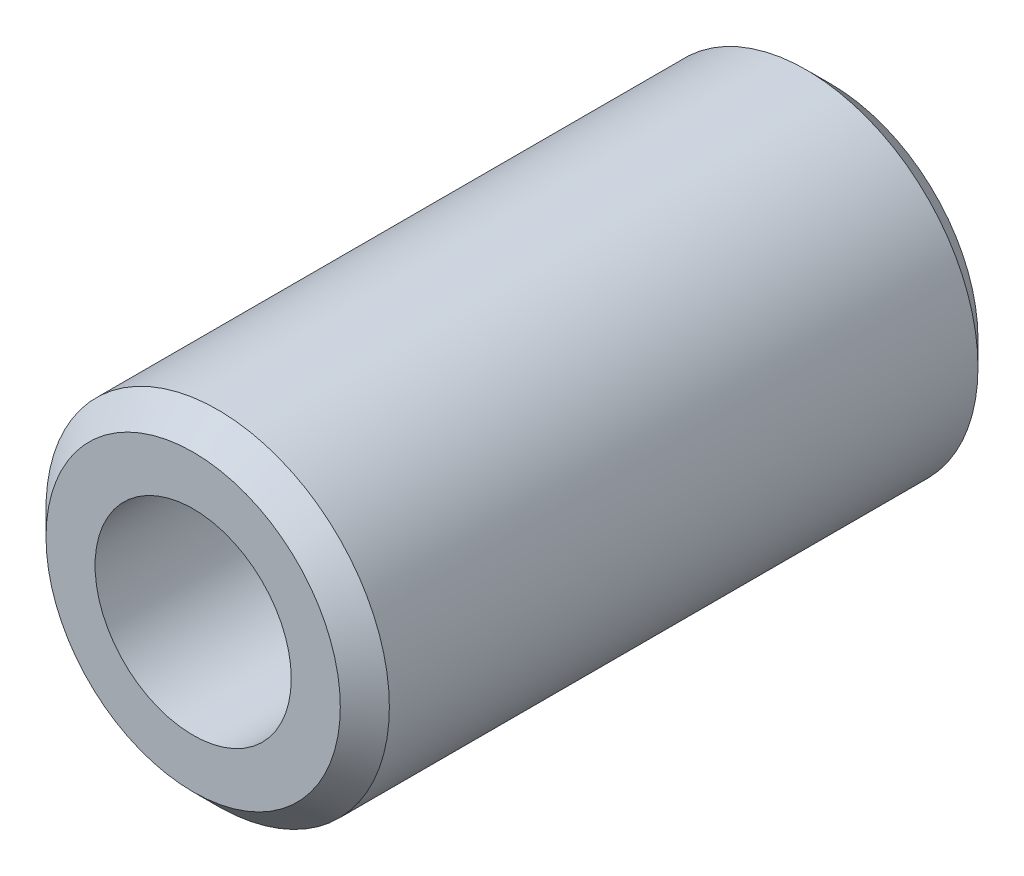
SolidWorks part; units mm, degrees
material "AISI 4340 Steel, normalized"
ref_plane "Front Plane" through (0, 0, 0) normal (0, 0, 1) x (1, 0, 0)
ref_plane "Top Plane" through (0, 0, 0) normal (0, 1, 0) x (1, 0, 0)
ref_plane "Right Plane" through (0, 0, 0) normal (1, 0, 0) x (0, 0, -1)
sketch "Sketch1" plane through (0, 0, 0) normal (0, 0, 1) x (1, 0, 0)
  circle A0 centre (0, 0) radius 17.5
  dimension "D1" = 35
extrude "Boss-Extrude1" add sketch "Sketch1" along normal blind 65
sketch "Sketch2" plane through (0, 0, 65) normal (0, 0, 1) x (1, 0, 0)
  circle A0 centre (0, 0) radius 10
  dimension "D1" = 20
extrude "Cut-Extrude1" cut sketch "Sketch2" against normal through all both and the other way through all
chamfer "Chamfer1" distance 2.5 angle 45 2 edges at (17.5, 0, 65) (17.5, 0, 0)
